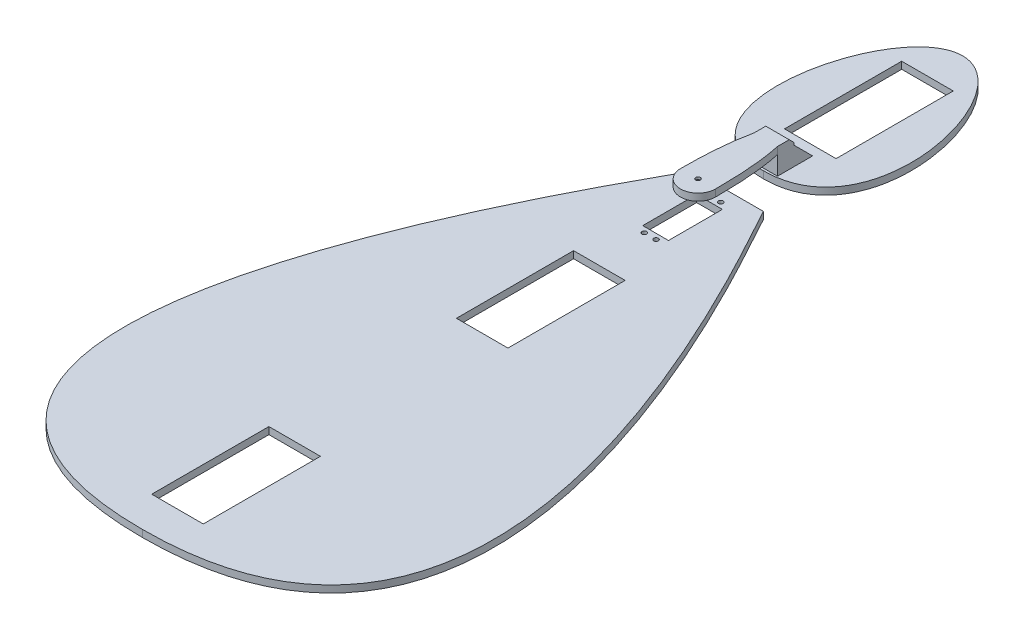
SolidWorks part; units mm, degrees
ref_plane "Plan de face" through (0, 0, 0) normal (0, 0, 1) x (1, 0, 0)
ref_plane "Plan de dessus" through (0, 0, 0) normal (0, 1, 0) x (1, 0, 0)
ref_plane "Plan de droite" through (0, 0, 0) normal (1, 0, 0) x (0, 0, -1)
sketch "Esquisse1" plane through (0, 0, 0) normal (0, 1, 0) x (1, 0, 0)
  line L0 (0, 0) -> (0, -105) construction
  line L1 (-11, 90) -> (11, 90)
  line L2 (-11, 90) -> (-11, 40)
  line L3 (-11, 40) -> (11, 40)
  line L4 (11, 90) -> (11, 40)
  line L5 (-11, -40) -> (11, -40)
  line L6 (-11, -40) -> (-11, -90)
  line L7 (-11, -90) -> (11, -90)
  line L8 (11, -40) -> (11, -90)
  line L9 (0, 0) -> (0, 145) construction
  line L10 (-75, 0) -> (75, 0) construction
  line L11 (-15, 145) -> (15, 145)
  line L12 (-67.1203, -105) -> (67.1203, -105) construction
  line L13 (-5.5, 125.5) -> (5.5, 125.5) construction
  line L14 (-5.5, 137) -> (5.5, 137)
  line L15 (-5.5, 137) -> (-5.5, 114)
  line L16 (-5.5, 114) -> (5.5, 114)
  line L17 (5.5, 137) -> (5.5, 114)
  line L18 (0, 145) -> (0, 240) construction
  circle A0 centre (-2.5, 139.3) radius 1
  circle A1 centre (2.5, 139.3) radius 1
  circle A2 centre (2.5, 111.7) radius 1
  circle A3 centre (-2.5, 111.7) radius 1
  spline S0 degree 3 poles (0, -105) (-166.9435, -105) (-16.6046, 139.7147) (-15, 145) knots 0 0 0 0 1 1 1 1
  spline S1 degree 3 poles (0, -105) (166.9435, -105) (16.6046, 139.7147) (15, 145) knots 0 0 0 0 1 1 1 1
  point P14 (0, 0)
  point P17 (0, 145)
  point P21 (0, -40)
  point P27 (0, 137)
  dimension "D13" = 2
  dimension "D1" = 22
  dimension "D2" = 50
  dimension "D3" = 22
  dimension "D4" = 50
  dimension "D5" = 80
  dimension "D6" = 150
  dimension "D7" = 30
  dimension "D8" = 15
  dimension "D9" = 250
  dimension "D10" = 40
  dimension "D11" = 11
  dimension "D12" = 23
  dimension "D14" = 2.3
  dimension "D15" = 2.5
  dimension "D16" = 8
extrude "Boss.-Extru.1" add sketch "Esquisse1" along normal blind 3
sketch "Esquisse2" plane through (0, 0, 0) normal (0, 1, 0) x (1, 0, 0)
  line L0 (0, 0) -> (0, 329.7823) construction
  line L1 (15, 145) -> (-15, 145) construction
  line L2 (-28.1695, 160) -> (28.1695, 160) construction
  line L3 (-11, 230) -> (11, 230)
  line L4 (-11, 230) -> (-11, 180)
  line L5 (-11, 180) -> (11, 180)
  line L6 (11, 230) -> (11, 180)
  line L7 (21.8829, 245) -> (-21.8829, 245) construction
  spline S0 degree 3 poles (0, 160) (-47.18, 160) (-27.6772, 245) (0, 245) knots 0 0 0 0 1 1 1 1
  spline S1 degree 3 poles (0, 160) (47.18, 160) (27.6772, 245) (0, 245) knots 0 0 0 0 1 1 1 1
  point P3 (0, 160)
  point P6 (0, 245)
  point P13 (0, 230)
  dimension "D1" = 15
  dimension "D2" = 85
  dimension "D3" = 22
  dimension "D4" = 50
  dimension "D5" = 15
extrude "Boss.-Extru.2" add sketch "Esquisse2" along normal blind 3 separate body
sketch "Esquisse3" plane through (0, 3, 0) normal (0, 1, 0) x (1, 0, 0)
  line L0 (0, 145) -> (0, 180) construction
  line L1 (15, 145) -> (-15, 145) construction
  line L2 (-11, 180) -> (11, 180) construction
  line L3 (-5, 176) -> (5, 176)
  line L4 (-5, 176) -> (-5, 161)
  line L5 (-5, 161) -> (5, 161)
  line L6 (5, 176) -> (5, 161)
  point P9 (0, 176)
  dimension "D1" = 10
  dimension "D2" = 15
  dimension "D3" = 4
extrude "Boss.-Extru.3" add sketch "Esquisse3" along normal blind 8
chamfer "Chanfrein1" distance 8 angle 45 1 edges at (0, 11, -176)
sketch "Esquisse4" plane through (0, 11, 0) normal (0, 1, 0) x (1, 0, 0)
  line L0 (0, 161) -> (0, 124.2832) construction
  line L1 (-5, 161) -> (5, 161) construction
  line L2 (-7.5, 132.1012) -> (7.5, 132.1012) construction
  line L3 (-5, 161) -> (-5, 168)
  line L4 (-5, 176) -> (-5, 161) construction
  line L5 (-5, 168) -> (-5, 161) construction
  line L6 (-5, 168) -> (5, 168)
  line L7 (5, 168) -> (5, 161)
  line L8 (-7.5, 143.7039) -> (-7.5, 120.4985) construction
  arc A0 (-7.5, 132.1012) -> (7.5, 132.1012) centre (0, 132.1012) ccw
  spline S0 degree 2 poles (-7.5, 132.1012) (-7.5, 149.9384) (-5, 161) knots 0 0 0 1 1 1
  spline S1 degree 2 poles (7.5, 132.1012) (7.5, 149.9384) (5, 161) knots 0 0 0 1 1 1
  dimension "D1" = 15
extrude "Boss.-Extru.4" add sketch "Esquisse4" along normal blind 3
chamfer "Chanfrein2" distance 2 angle 45 1 edges at (0, 14, -168)
sketch "Esquisse6" plane through (0, 11, 0) normal (0, -1, 0) x (1, 0, 0)
  circle A0 centre (0, -132.1012) radius 1
  dimension "D1" = 2
extrude "Enlèv. mat.-Extru.1" cut sketch "Esquisse6" against normal through all
sketch "Esquisse7" plane through (0, 11, 0) normal (0, -1, 0) x (1, 0, 0)
  circle A0 centre (0, -132.1012) radius 2
  dimension "D1" = 4
extrude "Enlèv. mat.-Extru.2" cut sketch "Esquisse7" against normal blind 2
sketch "Esquisse8" plane through (0, 11, 0) normal (0, -1, 0) x (1, 0, 0)
  circle A0 centre (0, -132.1012) radius 5
  circle A1 centre (0, -132.1012) radius 2
  dimension "D1" = 10
extrude "Boss.-Extru.6" add sketch "Esquisse8" along normal blind 3
chamfer "Chanfrein4" distance 2 angle 45 1 edges at (0, 8, -137.1012)
